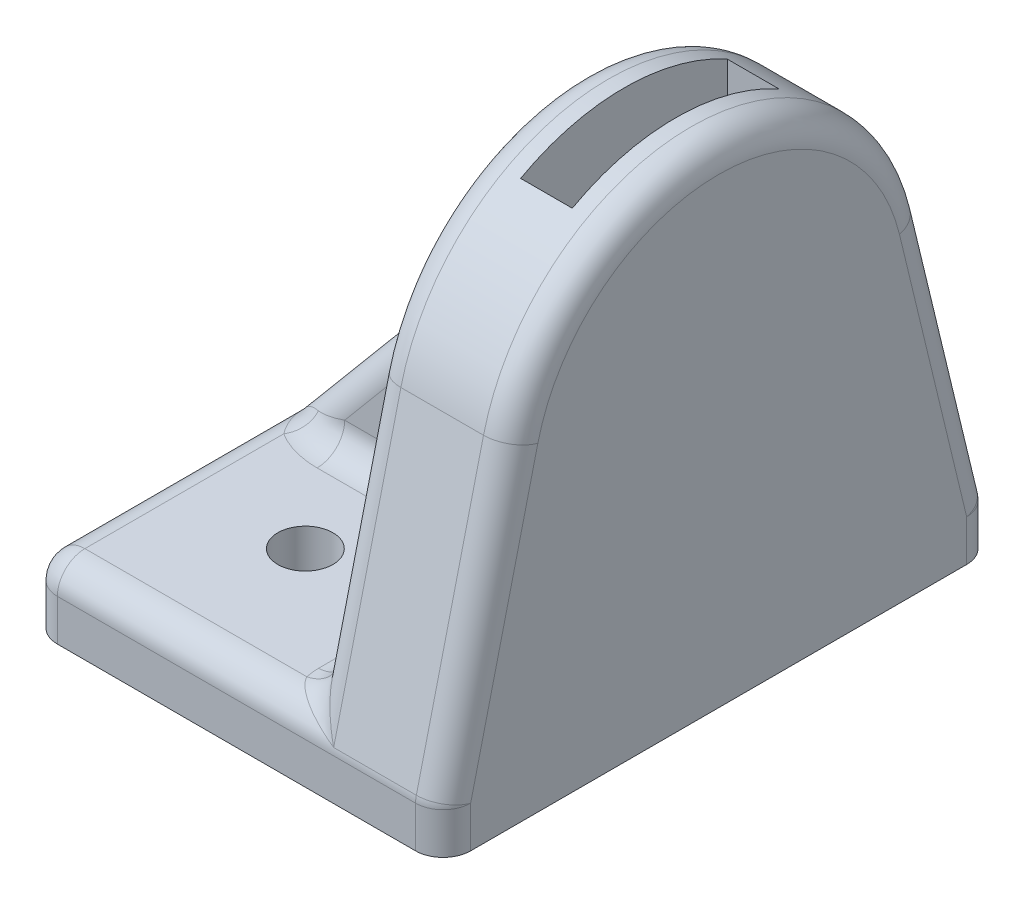
SolidWorks part; units mm, degrees
ref_plane "Front Plane" through (0, 0, 0) normal (0, 0, 1) x (1, 0, 0)
ref_plane "Top Plane" through (0, 0, 0) normal (0, 1, 0) x (1, 0, 0)
ref_plane "Right Plane" through (0, 0, 0) normal (1, 0, 0) x (0, 0, -1)
sketch "Sketch1" plane through (0, 0, 0) normal (0, 1, 0) x (1, 0, 0)
  line L1 (19.05, -25.4) -> (-19.05, -25.4)
  line L2 (19.05, -25.4) -> (19.05, 25.4)
  line L3 (19.05, 25.4) -> (-19.05, 25.4)
  line L4 (-19.05, -25.4) -> (-19.05, 25.4)
  line L5 (19.05, -25.4) -> (-19.05, 25.4) construction
  line L6 (19.05, 25.4) -> (-19.05, -25.4) construction
  circle A0 centre (-6.35, 12.7) radius 2.54
  circle A1 centre (-6.35, -12.7) radius 2.54
  point P0 (0, 0)
  dimension "D3" = 5.08
  dimension "D1" = 50.8
  dimension "D2" = 38.1
  dimension "D4" = 12.7
  dimension "D5" = 12.7
  dimension "D6" = 12.7
extrude "Boss-Extrude1" add sketch "Sketch1" along normal blind 6.35
fillet "Fillet1" radius 2.54 2 edges at (-19.05, 3.175, -25.4) (-19.05, 3.175, 25.4)
fillet "Fillet2" radius 2.54 5 edges at (1.27, 6.35, -25.4) (-18.3061, 6.35, -24.6561) (1.27, 6.35, 25.4) (-18.3061, 6.35, 24.6561) (-19.05, 6.35, 0)
sketch "Sketch2" plane through (19.05, 0, 0) normal (1, 0, 0) x (0, 0, -1)
  line L1 (-25.4, 0) -> (25.4, 0) construction
  line L2 (-19.1346, 30.0479) -> (-25.329, 4.4065)
  line L4 (25.329, 4.4065) -> (19.1346, 30.0479)
  line L5 (-22.86, 6.35) -> (22.86, 6.35) construction
  line L6 (-22.86, 6.35) -> (22.86, 6.35)
  arc A1 (19.1346, 30.0479) -> (-19.1346, 30.0479) centre (0, 25.4254) ccw
  arc A2 (25.4, 3.81) -> (22.86, 6.35) centre (22.86, 3.81) ccw construction
  arc A3 (-22.86, 6.35) -> (-25.4, 3.81) centre (-22.86, 3.81) ccw construction
  arc A4 (25.329, 4.4065) -> (22.86, 6.35) centre (22.86, 3.81) ccw
  arc A5 (-22.86, 6.35) -> (-25.329, 4.4065) centre (-22.86, 3.81) ccw
  dimension "D2" = 19.685
  dimension "D1" = 25.4254
extrude "Boss-Extrude2" add sketch "Sketch2" against normal blind 12.7
fillet "Fillet3" radius 2.54 10 edges at (6.35, 17.2272, -22.2318) (6.35, 17.2272, 22.2318) (19.05, 1.905, -25.4) (19.05, 4.1103, -25.3822) (19.05, 17.2272, -22.2318) (19.05, 1.905, 25.4) (19.05, 4.1103, 25.3822) (19.05, 17.2272, 22.2318) (6.35, 45.1104, 0) (19.05, 45.1104, 0)
sketch "Sketch7" plane through (0, 0, 0) normal (0, 0, 1) x (1, 0, 0)
  line L0 (6.35, 35.005) -> (-18.4558, 5.4427)
  line L1 (-16.51, 6.35) -> (6.421, 6.35) construction
  line L2 (6.35, 42.5704) -> (6.35, 29.4514) construction
  arc A0 (-16.51, 6.35) -> (-19.05, 3.81) centre (-16.51, 3.81) ccw construction
  dimension "D1" = 50
rib "Rib10" sketch "Sketch7" sketch "Sketch7" thickness 6.35 extrusion direction parallel to sketch draft on no parameters "D1"=6.35
fillet "Fillet4" radius 2.54 2 edges at (-6.0529, 20.2239, -3.175) (-6.0529, 20.2239, 3.175)
fillet "Fillet5" radius 2.54 17 edges at (-17.5835, 6.112, 1.7085) (-15.5127, 6.35, 3.0218) (7.3189, 5.8058, 24.4311) (6.3678, 6.35, 22.5554) (-17.5835, 6.112, -1.7085) (-15.5127, 6.35, -3.0218) (6.35, 18.7017, 3.175) (6.35, 33.8476, 2.4311) (6.35, 35.005, 0) (6.35, 33.8476, -2.4311) (7.3189, 5.8058, -24.4311) (6.3678, 6.35, -22.5554) (-4.0143, 6.35, 3.175) (6.35, 6.35, 12.7107) (-4.0143, 6.35, -3.175) (6.35, 18.7017, -3.175) (6.35, 6.35, -12.7107)
ref_plane "Plane1" through (12.7, 0, 0) normal (-1, 0, 0) x (0, 0, 1)
sketch "Sketch8" plane through (12.7, 0, 0) normal (-1, 0, 0) x (0, 0, 1)
  line L0 (9.525, 42.6525) -> (9.525, 25.4254)
  line L1 (-9.525, 42.6525) -> (-9.525, 25.4254)
  circle A0 centre (0, 25.4254) radius 9.525
  arc A1 (19.1346, 30.0479) -> (-19.1346, 30.0479) centre (0, 25.4254) ccw construction
  arc A2 (19.1346, 30.0479) -> (-19.1346, 30.0479) centre (0, 25.4254) ccw construction
  arc A3 (9.525, 42.6525) -> (-9.525, 42.6525) centre (0, 25.4254) ccw
  point P10 (-10.0195, 42.3697)
  point P12 (9.9177, 42.6525)
  dimension "D1" = 19.05
extrude "Cut-Extrude1" cut sketch "Sketch8" against normal mid plane 6.35 contours A0 region at (12.7, 25.4254, 0)
extrude "Cut-Extrude2" cut sketch "Sketch8<3>" against normal mid plane 4.7625 contours L0 A3 L1 A0 region at (12.7, 38.4345, 0)
sketch "Sketch8<3>" plane through (12.7, 0, 0) normal (-1, 0, 0) x (0, 0, 1) same geometry as "Sketch8"
